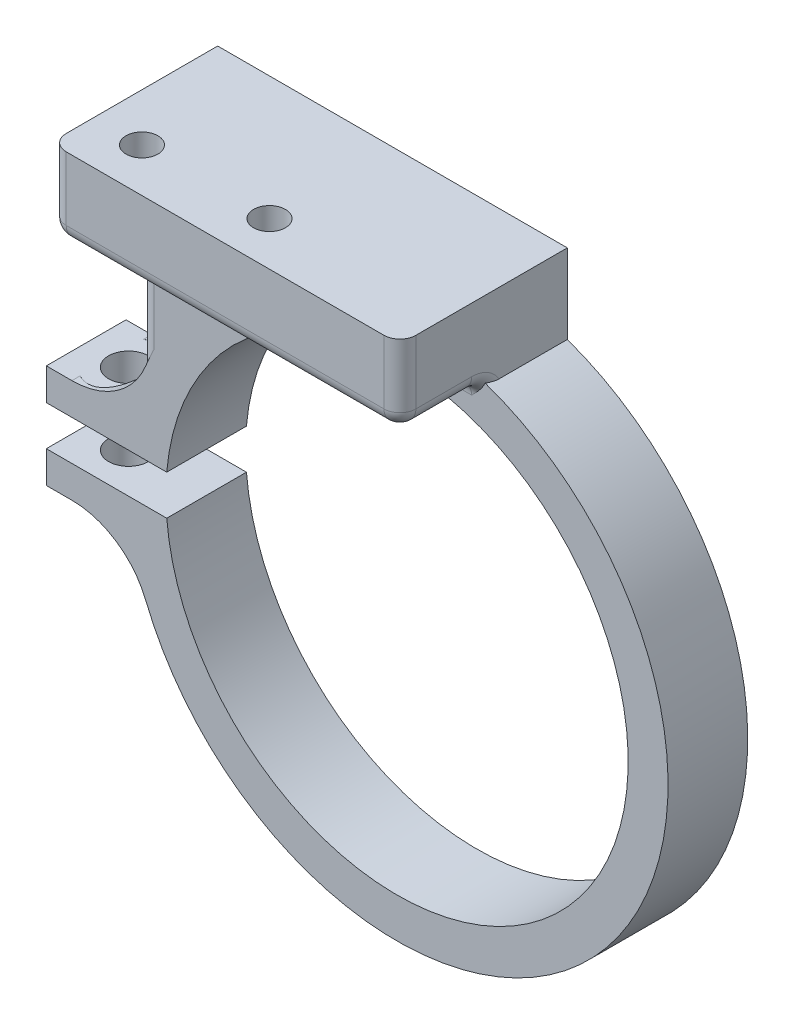
SolidWorks part; units mm, degrees
ref_plane "Front Plane" through (0, 0, 0) normal (0, 0, 1) x (1, 0, 0)
ref_plane "Top Plane" through (0, 0, 0) normal (0, 1, 0) x (1, 0, 0)
ref_plane "Right Plane" through (0, 0, 0) normal (1, 0, 0) x (0, 0, -1)
sketch "Sketch2" plane through (0, 0, 0) normal (0, 0, 1) x (1, 0, 0)
  line L0 (0, 0) -> (-34, 0) construction
  line L1 (-34, 0) -> (-44, 0) construction
  line L2 (-44, 0) -> (-44, -2.5) construction
  line L3 (-44, -2.5) -> (-33.908, -2.5)
  line L4 (-44, -2.5) -> (-44, -6.5)
  line L5 (-44, -6.5) -> (-33.3729, -6.5)
  line L6 (0, 0) -> (0, 6.0836)
  line L7 (-44, 2.5) -> (-33.908, 2.5)
  line L8 (-44, 2.5) -> (-44, 6.5)
  line L9 (-44, 6.5) -> (-33.3729, 6.5)
  line L10 (-33.908, -2.5) -> (-28.892, -2.5)
  line L11 (-33.908, 2.5) -> (-28.892, 2.5)
  line L15 (-32.5, 34) -> (-32.5, 42)
  line L21 (-32.5, 34) -> (-32.5, 9.9875)
  line L23 (11.364, 32.0446) -> (11.364, 42)
  line L24 (11.364, 42) -> (-32.5, 42)
  circle A0 centre (0, 0) radius 29
  arc A1 (-32.5, 9.9875) -> (32.5, 9.9875) centre (0, 0) ccw
  circle A2 centre (0, 0) radius 34 construction
  arc A3 (-32.5, 9.9875) -> (11.364, 32.0446) centre (0, 0) ccw
  arc A4 (32.5, 9.9875) -> (11.364, 32.0446) centre (0, 0) ccw
  point P19 (-32.5, 38)
  point P21 (0, 34)
  point P25 (0, 49.2735)
  dimension "D1" = 58
  dimension "D2" = 10
  dimension "D3" = 2.5
  dimension "D5" = 4
  dimension "D6" = 43.864
  dimension "D7" = 8
  dimension "D4" = 5
extrude "Boss-Extrude3" add sketch "Sketch2" along normal blind 10 contours A1 L11 A0 L10 | A1 L9 L8 L7 | A1 L3 L4 L5 | A1 region at (-38.8392, -4.5173, 0) region at (-31.4, -3.5192, 0) region at (-38.8392, 4.5173, 0)
sketch "Sketch3" plane through (0, 0, 0) normal (0, 0, -1) x (-1, 0, 0)
  line L0 (32.5, 9.9875) -> (32.5, 42) construction
  line L1 (-11.364, 42) -> (32.5, 42)
  line L2 (-11.364, 42) -> (-11.364, 32)
  line L3 (-11.364, 32) -> (32.5, 32)
  line L4 (32.5, 42) -> (32.5, 32)
  dimension "D1" = 10
extrude "Boss-Extrude4" add sketch "Sketch3" against normal blind 21
sketch "Sketch4" plane through (0, 32, 0) normal (0, -1, 0) x (1, 0, 0)
  line L0 (-32.5, 21) -> (-32.5, 10) construction
  circle A0 centre (-26.5, 15.5) radius 2
  circle A1 centre (-10.5, 15.5) radius 2
  point P7 (-32.5, 15.5)
  dimension "D1" = 4
  dimension "D2" = 4
  dimension "D3" = 6
  dimension "D4" = 16
extrude "Cut-Extrude1" cut sketch "Sketch4" against normal through all
sketch "Sketch5" plane through (0, 32, 0) normal (0, -1, 0) x (1, 0, 0)
  circle A0 centre (-26.5, 15.5) radius 3.5
  circle A1 centre (-10.5, 15.5) radius 3.5
  dimension "D1" = 7
  dimension "D2" = 7
extrude "Cut-Extrude2" cut sketch "Sketch5" against normal blind 4
fillet "Fillet1" radius 2 1 edges at (-10.568, 32, 10) type face fillet first side face at (-26.5, 32, 12) second side face at (-20.9799, 5.6261, 10)
fillet "Fillet2" radius 2 1 edges at (11.364, 32, 16.5) type face fillet first side face at (11.364, 34.6434, 10.5123) second side face at (-14.534, 32, 14.25)
fillet "Fillet3" radius 2 1 edges at (-32.5, 32, 16.5) type face fillet first side face at (-32.5, 28.3413, 10.5123) second side face at (-15.034, 32, 14.25)
fillet "Fillet4" radius 2 1 edges at (-10.568, 32, 21) type face fillet first side face at (-10.568, 35.8619, 21) second side face at (-14.534, 32, 14.25)
sketch "Sketch6" plane through (0, -6.5, 0) normal (0, -1, 0) x (1, 0, 0)
  line L0 (-44, 10) -> (-44, 0) construction
  line L1 (-44, 0) -> (-33.3729, 0) construction
  circle A0 centre (-38.6864, 5) radius 2.5
  point P4 (-44, 5)
  point P7 (-38.6864, 0)
  dimension "D1" = 5
extrude "Cut-Extrude3" cut sketch "Sketch6" against normal through all both and the other way through all
fillet "Fillet5" radius 10 1 edges at (-33.3729, -6.5, 5)
fillet "Fillet6" radius 10 1 edges at (-33.3729, 6.5, 5)
sketch "Sketch7" plane through (0, -6.5, 0) normal (0, -1, 0) x (1, 0, 0)
  circle A0 centre (-38.6864, 5) radius 4.5
  dimension "D1" = 9
extrude "Cut-Extrude4" cut sketch "Sketch7" along normal blind 10
sketch "Sketch8" plane through (0, 6.5, 0) normal (0, 1, 0) x (1, 0, 0)
  circle A0 centre (-38.6864, -5) radius 4.5
  dimension "D1" = 9
extrude "Cut-Extrude5" cut sketch "Sketch8" along normal blind 10
